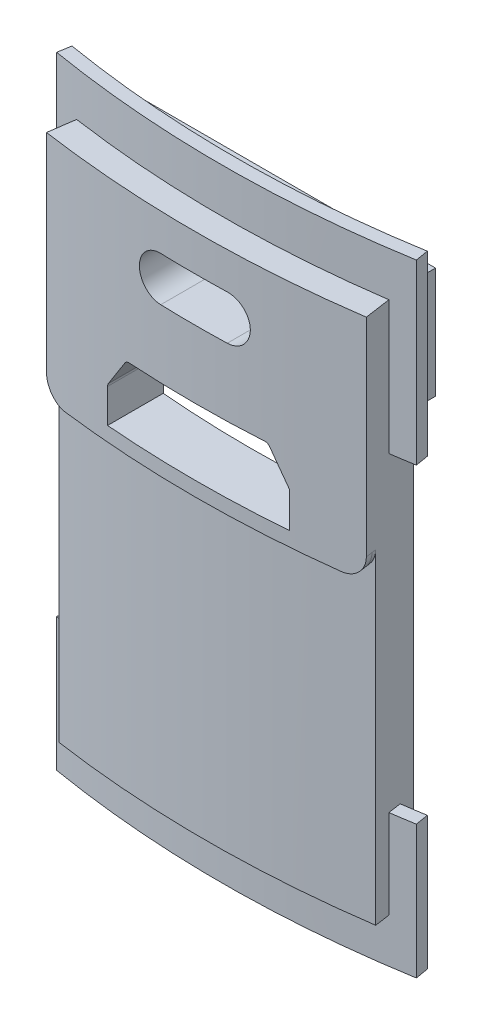
SolidWorks part; units mm, degrees
material "ABS"
ref_plane "Front Plane" through (0, 0, 0) normal (0, 0, 1) x (1, 0, 0)
ref_plane "Top Plane" through (0, 0, 0) normal (0, 1, 0) x (1, 0, 0)
ref_plane "Right Plane" through (0, 0, 0) normal (1, 0, 0) x (0, 0, -1)
sketch "Эскиз1" plane through (0, 0, 0) normal (0, 1, 0) x (1, 0, 0)
  line L0 (-6.8438, 0.4925) -> (-7.1588, -1.6849)
  line L1 (6.8438, 0.4925) -> (7.1588, -1.6849)
  arc A0 (-6.8438, 0.4925) -> (6.8438, 0.4925) centre (0, 47.8) ccw
  arc A1 (-7.1588, -1.6849) -> (7.1588, -1.6849) centre (0, 47.8) ccw
extrude "Бобышка-Вытянуть1" add sketch "Эскиз1" along normal blind 24
sketch "Эскиз2" plane through (0, 0, 0) normal (0, 0, 1) x (1, 0, 0)
  line L8 (3.05, 17.3) -> (-3.05, 17.3)
  line L9 (4.0595, 15.9585) -> (3.2596, 17.1864)
  line L10 (-3.2596, 17.1864) -> (-4.0595, 15.9585)
  line L11 (-4.1, 14.788) -> (-4.1, 15.8219)
  line L12 (4.1, 14.788) -> (4.1, 15.8219)
  line L13 (-4.1, 14.3) -> (4.1, 14.3)
  line L14 (-4.1, 14.788) -> (-4.1, 14.3)
  line L15 (4.1, 14.788) -> (4.1, 14.3)
  line L16 (5.5897, 21.35) -> (-4.3329, 21.35) construction
  line L17 (-1.5632, 22.35) -> (-1.5632, 20.35) construction
  line L18 (1.4368, 22.35) -> (1.4368, 20.35) construction
  line L19 (-0.0632, 22.35) -> (0, 0) construction
  line L20 (-0.0632, 22.35) -> (1.4368, 22.35)
  line L21 (-0.0632, 22.35) -> (-1.5632, 22.35)
  line L23 (-1.5632, 20.35) -> (1.4368, 20.35)
  arc A4 (3.05, 17.3) -> (3.2596, 17.1864) centre (3.05, 17.0498) cw
  arc A5 (-3.2596, 17.1864) -> (-3.05, 17.3) centre (-3.05, 17.0498) cw
  arc A6 (-4.0595, 15.9585) -> (-4.1, 15.8219) centre (-3.8498, 15.8219) ccw
  arc A7 (4.0595, 15.9585) -> (4.1, 15.8219) centre (3.8498, 15.8219) cw
  arc A12 (-1.5632, 22.35) -> (-1.5632, 20.35) centre (-1.5632, 21.35) ccw
  arc A13 (1.4368, 20.35) -> (1.4368, 22.35) centre (1.4368, 21.35) ccw
  point P0 (0, 17.3)
  point P19 (0, 14.3)
  point P21 (-2.5632, 21.35)
  point P23 (2.4368, 21.35)
extrude "Вырез-Вытянуть2" cut sketch "Эскиз2" along normal blind 5 and the other way blind 5
sketch "Эскиз3" plane through (0, 24, 0) normal (0, 1, 0) x (1, 0, 0)
  line L1 (-8.0011, -0.0355) -> (-8.1001, -0.6272)
  line L3 (8.0011, -0.0355) -> (8.1001, -0.6272)
  line L4 (0, -0.7) -> (0, 0) construction
  line L5 (-6.8438, 0.4925) -> (-7.1588, -1.6849) construction
  line L6 (-6.9441, -0.2003) -> (-7.03, -0.7941)
  line L7 (7.1588, -1.6849) -> (6.8438, 0.4925) construction
  line L8 (7.03, -0.7941) -> (6.9441, -0.2003)
  arc A0 (-8.0011, -0.0355) -> (-6.9441, -0.2003) centre (0, 47.8) ccw
  arc A1 (-8.1001, -0.6272) -> (-7.03, -0.7941) centre (0, 47.8) ccw
  arc A2 (7.03, -0.7941) -> (8.1001, -0.6272) centre (0, 47.8) ccw
  arc A3 (6.9441, -0.2003) -> (8.0011, -0.0355) centre (0, 47.8) ccw
extrude "Бобышка-Вытянуть2" add sketch "Эскиз3" against normal up to surface (24 mm away) up to face at (0, 0, 0.8481)
sketch "Эскиз4" plane through (0, 24, 0) normal (0, 1, 0) x (1, 0, 0)
  line L0 (-8.0011, -0.0355) -> (-8.1001, -0.6272)
  line L2 (8.0011, -0.0355) -> (8.1001, -0.6272)
  line L3 (0, -0.7) -> (0, 0) construction
  arc A0 (-8.0011, -0.0355) -> (8.0011, -0.0355) centre (0, 47.8) ccw
  arc A1 (-8.1001, -0.6272) -> (8.1001, -0.6272) centre (0, 47.8) ccw
extrude "Бобышка-Вытянуть3" add sketch "Эскиз4" along normal blind 2
sketch "Эскиз5" plane through (0, 0, 0) normal (0, -1, 0) x (1, 0, 0)
  line L0 (8.0011, 0.0355) -> (8.1001, 0.6272)
  line L1 (-8.0011, 0.0355) -> (-8.1001, 0.6272)
  line L2 (0, 0.7) -> (0, 0) construction
  arc A0 (8.0011, 0.0355) -> (-8.0011, 0.0355) centre (0, -47.8) ccw
  arc A1 (8.1001, 0.6272) -> (-8.1001, 0.6272) centre (0, -47.8) ccw
extrude "Бобышка-Вытянуть4" add sketch "Эскиз5" along normal blind 2
sketch "Эскиз6" plane through (0, 0, 0) normal (0, -1, 0) x (1, 0, 0)
  line L0 (-7.1588, 1.6849) -> (-7.1302, 1.4869)
  line L1 (7.1588, 1.6849) -> (7.1302, 1.4869)
  arc A0 (7.1588, 1.6849) -> (-7.1588, 1.6849) centre (0, -47.8) ccw construction
  arc A1 (7.1588, 1.6849) -> (-7.1588, 1.6849) centre (0, -47.8) ccw
  arc A2 (7.1302, 1.4869) -> (-7.1302, 1.4869) centre (0, -47.8) ccw
  dimension "D1" = 0.2
extrude "Вырез-Вытянуть3" cut sketch "Эскиз6" against normal blind 13.65
fillet "Скругление1" radius 1 2 edges at (-7.1445, 13.65, 1.5859) (7.1445, 13.65, 1.5859)
sketch "Эскиз8" plane through (0, 26, 0) normal (0, 1, 0) x (1, 0, 0)
  line L0 (8.1001, -0.6272) -> (8.0011, -0.0355) construction
  line L1 (-8.0011, -0.0355) -> (-8.1001, -0.6272) construction
  line L2 (8.1001, -0.6272) -> (8.0011, -0.0355)
  line L3 (-8.0011, -0.0355) -> (-8.1001, -0.6272)
  line L4 (-6.9441, -0.2003) -> (-7.03, -0.7941)
  line L5 (6.9441, -0.2003) -> (7.03, -0.7941)
  arc A0 (-8.0011, -0.0355) -> (8.0011, -0.0355) centre (0, 47.8) ccw construction
  arc A1 (-8.1001, -0.6272) -> (8.1001, -0.6272) centre (0, 47.8) ccw construction
  arc A2 (-8.0011, -0.0355) -> (-6.9441, -0.2003) centre (0, 47.8) ccw
  arc A3 (-8.1001, -0.6272) -> (-7.03, -0.7941) centre (0, 47.8) ccw
  arc A4 (7.03, -0.7941) -> (8.1001, -0.6272) centre (0, 47.8) ccw
  arc A5 (6.9441, -0.2003) -> (8.0011, -0.0355) centre (0, 47.8) ccw
extrude "Вырез-Вытянуть5" cut sketch "Эскиз8" against normal blind 14 from offset 8 offset against normal yes
sketch "Эскиз9" plane through (0, 24, 0) normal (0, 1, 0) x (1, 0, 0)
  line L0 (-6.8438, 0.4925) -> (-6.8438, 1.4925)
  line L1 (6.8438, 0.4925) -> (6.8438, 1.4925)
  line L2 (6.8438, 1.4925) -> (-6.8438, 1.4925)
  arc A0 (-6.8438, 0.4925) -> (6.8438, 0.4925) centre (0, 47.8) ccw construction
  arc A1 (-6.8438, 0.4925) -> (6.8438, 0.4925) centre (0, 47.8) ccw
extrude "Бобышка-Вытянуть5" add sketch "Эскиз9" against normal blind 5
sketch "Эскиз10" plane through (0, 0, 0) normal (0, 0, 1) x (1, 0, 0)
  line L0 (1.4368, 20.35) -> (-1.5632, 20.35) construction
  line L1 (-1.5632, 22.35) -> (1.4368, 22.35) construction
  line L2 (1.4368, 20.35) -> (-1.5632, 20.35)
  line L3 (-1.5632, 22.35) -> (1.4368, 22.35)
  arc A2 (1.4368, 20.35) -> (1.4368, 22.35) centre (1.4368, 21.35) ccw construction
  arc A3 (-1.5632, 22.35) -> (-1.5632, 20.35) centre (-1.5632, 21.35) ccw construction
  arc A4 (1.4368, 20.35) -> (1.4368, 22.35) centre (1.4368, 21.35) ccw
  arc A5 (-1.5632, 22.35) -> (-1.5632, 20.35) centre (-1.5632, 21.35) ccw
extrude "Вырез-Вытянуть6" cut sketch "Эскиз10" against normal up to surface (1.4925 mm away) up to face at (0, 21.5, -1.4925)
sketch "Эскиз11" plane through (0, 24, 0) normal (0, 1, 0) x (1, 0, 0)
  line L0 (-7.1588, -1.6849) -> (-7.2018, -1.9818)
  line L1 (7.1588, -1.6849) -> (7.2018, -1.9818)
  line L2 (-7.03, -0.7941) -> (-7.1588, -1.6849) construction
  arc A0 (-7.1588, -1.6849) -> (7.1588, -1.6849) centre (0, 47.8) ccw construction
  arc A1 (-7.1588, -1.6849) -> (7.1588, -1.6849) centre (0, 47.8) ccw
  arc A2 (-7.2018, -1.9818) -> (7.2018, -1.9818) centre (0, 47.8) ccw
  dimension "D1" = 50.3
extrude "Бобышка-Вытянуть6" add sketch "Эскиз11" against normal up to surface (10.35 mm away) up to face at (0, 13.65, 1.9096)
fillet "Скругление2" radius 1 2 edges at (7.1803, 13.65, 1.8333) (-7.1803, 13.65, 1.8333)
sketch "Эскиз12" plane through (0, 0, -1.4925) normal (0, 0, -1) x (-1, 0, 0)
  line L0 (1.5632, 20.35) -> (-1.4368, 20.35) construction
  line L1 (-1.4368, 22.35) -> (1.5632, 22.35) construction
  line L2 (1.5632, 20.35) -> (-1.4368, 20.35)
  line L3 (-1.4368, 22.35) -> (1.5632, 22.35)
  line L4 (4.1, 14.3) -> (4.1, 15.8219) construction
  line L5 (3.2596, 17.1864) -> (4.0595, 15.9585) construction
  line L6 (-3.05, 17.3) -> (3.05, 17.3) construction
  line L7 (4.1, 14.3) -> (-4.1, 14.3) construction
  line L8 (-4.1, 15.8219) -> (-4.1, 14.3) construction
  line L9 (-4.0595, 15.9585) -> (-3.2596, 17.1864) construction
  line L10 (4.1, 14.3) -> (4.1, 15.8219)
  line L11 (3.2596, 17.1864) -> (4.0595, 15.9585)
  line L12 (-3.05, 17.3) -> (3.05, 17.3)
  line L13 (4.1, 14.3) -> (-4.1, 14.3)
  line L14 (-4.1, 15.8219) -> (-4.1, 14.3)
  line L15 (-4.0595, 15.9585) -> (-3.2596, 17.1864)
  arc A0 (1.5632, 20.35) -> (1.5632, 22.35) centre (1.5632, 21.35) ccw construction
  arc A1 (-1.4368, 22.35) -> (-1.4368, 20.35) centre (-1.4368, 21.35) ccw construction
  arc A2 (1.5632, 20.35) -> (1.5632, 22.35) centre (1.5632, 21.35) ccw
  arc A3 (-1.4368, 22.35) -> (-1.4368, 20.35) centre (-1.4368, 21.35) ccw
  arc A4 (4.1, 15.8219) -> (4.0595, 15.9585) centre (3.8498, 15.8219) ccw construction
  arc A5 (3.2596, 17.1864) -> (3.05, 17.3) centre (3.05, 17.0498) ccw construction
  arc A6 (-4.0595, 15.9585) -> (-4.1, 15.8219) centre (-3.8498, 15.8219) ccw construction
  arc A7 (-3.05, 17.3) -> (-3.2596, 17.1864) centre (-3.05, 17.0498) ccw construction
  arc A8 (4.1, 15.8219) -> (4.0595, 15.9585) centre (3.8498, 15.8219) ccw
  arc A9 (3.2596, 17.1864) -> (3.05, 17.3) centre (3.05, 17.0498) ccw
  arc A10 (-4.0595, 15.9585) -> (-4.1, 15.8219) centre (-3.8498, 15.8219) ccw
  arc A11 (-3.05, 17.3) -> (-3.2596, 17.1864) centre (-3.05, 17.0498) ccw
extrude "Вырез-Вытянуть7" cut sketch "Эскиз12" against normal blind 5
